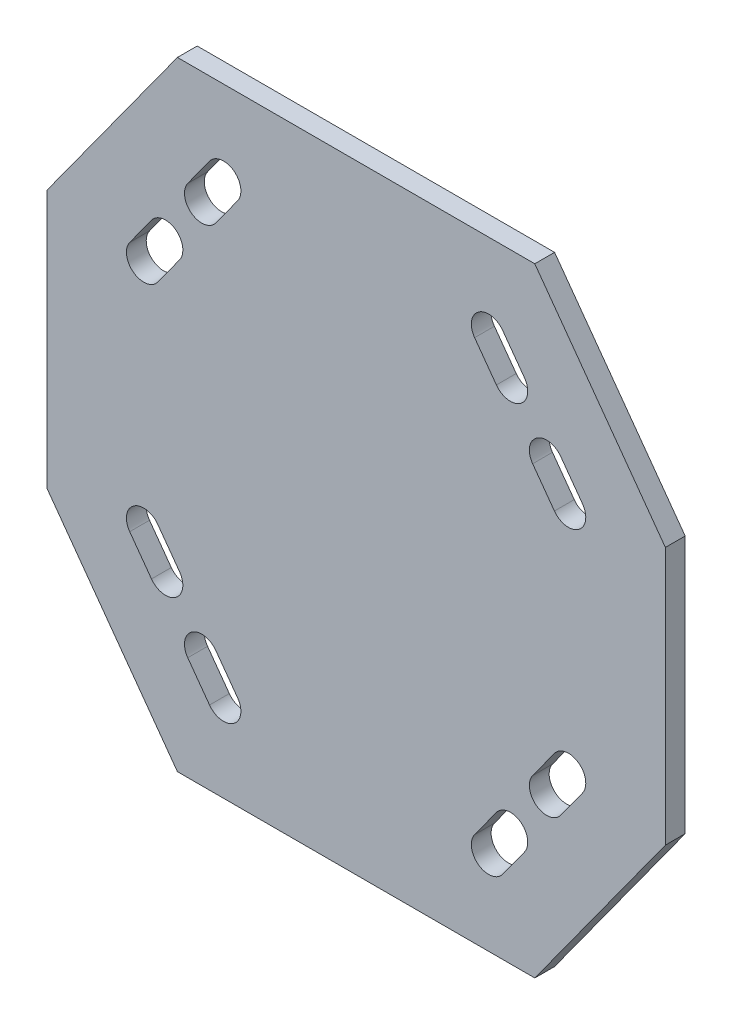
SolidWorks part; units mm, degrees
material "Простая углеродистая сталь"
ref_plane "Спереди" through (0, 0, 0) normal (0, 0, 1) x (1, 0, 0)
ref_plane "Сверху" through (0, 0, 0) normal (0, 1, 0) x (1, 0, 0)
ref_plane "Справа" through (0, 0, 0) normal (1, 0, 0) x (0, 0, -1)
sketch "Эскиз1" plane through (0, 0, 0) normal (0, 0, 1) x (1, 0, 0)
  line L1 (0, 0) -> (250, 0)
  line L2 (0, 0) -> (0, -250)
  line L3 (0, -250) -> (250, -250)
  line L4 (250, 0) -> (250, -250)
  dimension "D1" = 250
  dimension "D2" = 250
base flange "Базовая кромка1" sketch "Эскиз1" thickness 8 reverse thickness direction no parameters "D1"=1
sketch "Эскиз2" plane through (0, 0, 0) normal (0, 0, 1) x (1, 0, 0)
  line L0 (52.7787, 0) -> (0, -72.9)
  line L1 (250, 0) -> (0, 0) construction
  line L2 (0, -72.9) -> (0, 0)
  line L3 (0, 0) -> (52.7787, 0)
  line L4 (125, 0) -> (125, -75.5488) construction
  line L5 (250, 0) -> (197.2213, 0)
  line L6 (250, -72.9) -> (250, 0)
  line L7 (197.2213, 0) -> (250, -72.9)
  line L8 (0, -125) -> (66.8204, -125) construction
  line L9 (0, 0) -> (0, -250) construction
  line L10 (197.2213, -250) -> (250, -177.1)
  line L11 (250, -177.1) -> (250, -250)
  line L12 (250, -250) -> (197.2213, -250)
  line L13 (0, -250) -> (52.7787, -250)
  line L14 (0, -177.1) -> (0, -250)
  line L15 (52.7787, -250) -> (0, -177.1)
  dimension "D1" = 90
  dimension "D2" = 72.9
extrude "Вырез-Вытянуть1" cut sketch "Эскиз2" against normal blind 10 normal cut yes
sketch "Эскиз3" plane through (0, 0, -8) normal (0, 0, -1) x (-1, 0, 0)
  line L0 (-71.4273, -33.925) -> (-62.6308, -46.075) construction
  line L1 (-65.7573, -29.82) -> (-56.9608, -41.97)
  line L2 (-77.0973, -38.03) -> (-68.3008, -50.18)
  line L3 (0, -72.9) -> (-52.7787, 0) construction
  line L4 (-47.9701, -66.325) -> (-39.1736, -78.475) construction
  line L5 (-42.3001, -62.22) -> (-33.5036, -74.37)
  line L6 (-53.6401, -70.43) -> (-44.8436, -82.58)
  line L7 (-125, 0) -> (-125, -250) construction
  line L8 (-197.2213, 0) -> (-52.7787, 0) construction
  line L9 (-52.7787, -250) -> (-197.2213, -250) construction
  line L10 (0, -125) -> (-77.0868, -125) construction
  line L11 (0, -72.9) -> (0, -177.1) construction
  line L12 (-178.5727, -33.925) -> (-187.3692, -46.075) construction
  line L13 (-184.2427, -29.82) -> (-193.0392, -41.97)
  line L14 (-172.9027, -38.03) -> (-181.6992, -50.18)
  line L15 (-202.0299, -66.325) -> (-210.8264, -78.475) construction
  line L16 (-207.6999, -62.22) -> (-216.4964, -74.37)
  line L17 (-196.3599, -70.43) -> (-205.1564, -82.58)
  line L18 (-71.4273, -216.075) -> (-62.6308, -203.925) construction
  line L19 (-65.7573, -220.18) -> (-56.9608, -208.03)
  line L20 (-77.0973, -211.97) -> (-68.3008, -199.82)
  line L21 (-47.9701, -183.675) -> (-39.1736, -171.525) construction
  line L22 (-42.3001, -187.78) -> (-33.5036, -175.63)
  line L23 (-53.6401, -179.57) -> (-44.8436, -167.42)
  line L24 (-178.5727, -216.075) -> (-187.3692, -203.925) construction
  line L25 (-184.2427, -220.18) -> (-193.0392, -208.03)
  line L26 (-172.9027, -211.97) -> (-181.6992, -199.82)
  line L27 (-202.0299, -183.675) -> (-210.8264, -171.525) construction
  line L28 (-207.6999, -187.78) -> (-216.4964, -175.63)
  line L29 (-196.3599, -179.57) -> (-205.1564, -167.42)
  arc A0 (-65.7573, -29.82) -> (-77.0973, -38.03) centre (-71.4273, -33.925) ccw
  arc A1 (-68.3008, -50.18) -> (-56.9608, -41.97) centre (-62.6308, -46.075) ccw
  arc A2 (-42.3001, -62.22) -> (-53.6401, -70.43) centre (-47.9701, -66.325) ccw
  arc A3 (-44.8436, -82.58) -> (-33.5036, -74.37) centre (-39.1736, -78.475) ccw
  arc A4 (-184.2427, -29.82) -> (-172.9027, -38.03) centre (-178.5727, -33.925) cw
  arc A5 (-181.6992, -50.18) -> (-193.0392, -41.97) centre (-187.3692, -46.075) cw
  arc A6 (-207.6999, -62.22) -> (-196.3599, -70.43) centre (-202.0299, -66.325) cw
  arc A7 (-205.1564, -82.58) -> (-216.4964, -74.37) centre (-210.8264, -78.475) cw
  arc A8 (-65.7573, -220.18) -> (-77.0973, -211.97) centre (-71.4273, -216.075) cw
  arc A9 (-68.3008, -199.82) -> (-56.9608, -208.03) centre (-62.6308, -203.925) cw
  arc A10 (-42.3001, -187.78) -> (-53.6401, -179.57) centre (-47.9701, -183.675) cw
  arc A11 (-44.8436, -167.42) -> (-33.5036, -175.63) centre (-39.1736, -171.525) cw
  arc A12 (-184.2427, -220.18) -> (-172.9027, -211.97) centre (-178.5727, -216.075) ccw
  arc A13 (-181.6992, -199.82) -> (-193.0392, -208.03) centre (-187.3692, -203.925) ccw
  arc A14 (-207.6999, -187.78) -> (-196.3599, -179.57) centre (-202.0299, -183.675) ccw
  arc A15 (-205.1564, -167.42) -> (-216.4964, -175.63) centre (-210.8264, -171.525) ccw
  point P2 (-67.0291, -40)
  point P12 (-43.5719, -72.4)
  point P29 (-182.9709, -40)
  point P36 (-206.4281, -72.4)
  point P43 (-67.0291, -210)
  point P50 (-43.5719, -177.6)
  point P57 (-182.9709, -210)
  point P64 (-206.4281, -177.6)
  dimension "D1" = 7
  dimension "D4" = 15
  dimension "D2" = 35
  dimension "D3" = 40
  dimension "D5" = 40
extrude "Вырез-Вытянуть2" cut sketch "Эскиз3" against normal blind 10 normal cut yes
sketch "Сгиб-Линии1" [suppressed] plane through (0, 0, 0) normal (0, 1, 0) x (1, 0, 0)
sketch "Граничная рамка1" [suppressed] plane through (0, 0, 0) normal (0, 1, 0) x (1, 0, 0)
sheet metal parameters "Листовой металл1" thickness 8 parameters "D1"=1
flat pattern "Развертка1" [suppressed]
sketch "Сгиб-Линии2" plane through (0, 0, 0) normal (0, 1, 0) x (1, 0, 0)
sketch "Граничная рамка2" [suppressed] plane through (0, 0, 0) normal (0, 1, 0) x (1, 0, 0)
sheet metal parameters "Листовой металл2" thickness 8 parameters "D1"=1
flat pattern "Развертка1"
sketch "Сгиб-Линии2" plane through (0, 0, 0) normal (0, 1, 0) x (1, 0, 0)
sketch "Граничная рамка2" [suppressed] plane through (0, 0, 0) normal (0, 1, 0) x (1, 0, 0)
sheet metal parameters "Листовой металл3" thickness 8 parameters "D1"=1
flat pattern "Развертка1"
sketch "Сгиб-Линии2" plane through (0, 0, 0) normal (0, 1, 0) x (1, 0, 0)
sketch3d "Граничная рамка2" [suppressed]
  line L0 (0, -250, 0) -> (250, -250, 0) construction
  line L1 (0, 0, 0) -> (250, 0, 0) construction
  line L2 (0, -250, 0) -> (0, 0, 0) construction
  line L3 (250, -250, 0) -> (250, 0, 0) construction
